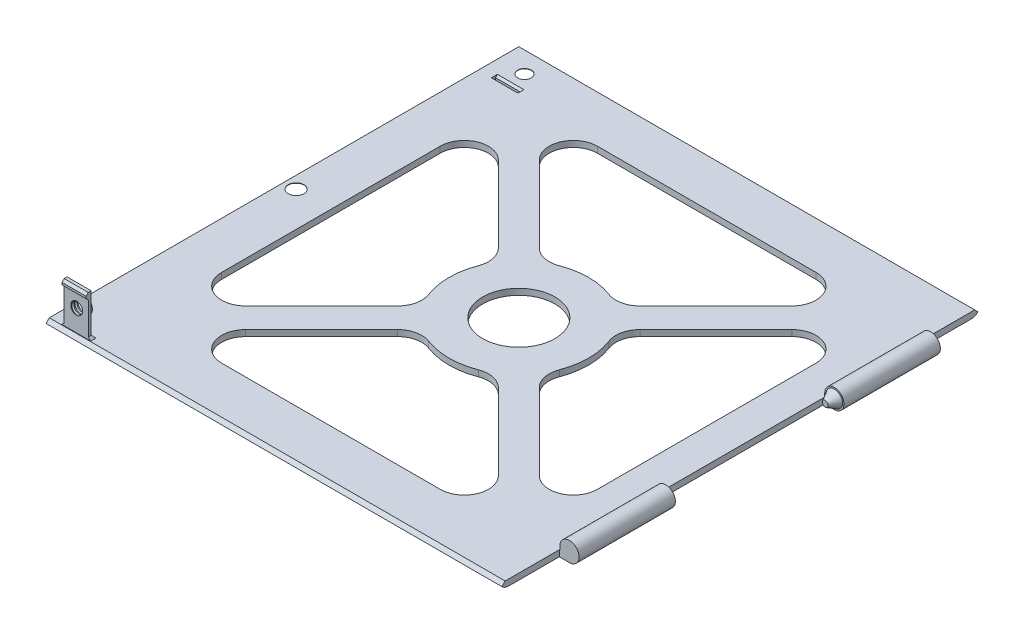
SolidWorks part; units mm, degrees
material "6061 Alloy"
ref_plane "Front Plane" through (0, 0, 0) normal (0, 0, 1) x (1, 0, 0)
ref_plane "Top Plane" through (0, 0, 0) normal (0, 1, 0) x (1, 0, 0)
ref_plane "Right Plane" through (0, 0, 0) normal (1, 0, 0) x (0, 0, -1)
sketch "X-Axis" plane through (0, 0, 0) normal (0, 1, 0) x (1, 0, 0)
  line L2 (-10, 0) -> (10, 0)
  point P3 (0, 0)
  dimension "D1" = 20
sketch "Y-Axis" plane through (0, 0, 0) normal (0, 1, 0) x (1, 0, 0)
  line L0 (0, -10) -> (0, 10)
  dimension "D1" = 20
sketch "Z-Axis" plane through (0, 0, 0) normal (1, 0, 0) x (0, 0, -1)
  line L0 (0, 10) -> (0, -10)
  line L1 (0, 55) -> (0, -55) construction
  point P5 (0, 0)
  dimension "D1" = 20
ref_axis "Axis1" through (0, 0, 0) along (0, 1, 0)
sketch "Sketch1" plane through (0, 0, 0) normal (0, 1, 0) x (1, 0, 0)
  line L0 (-10.4535, 14.6961) -> (-26.2218, 30.4645)
  line L1 (-46, -46) -> (46, -46) construction
  line L2 (-46, -46) -> (-46, 46) construction
  line L3 (-46, 46) -> (46, 46) construction
  line L4 (46, -46) -> (46, 46) construction
  line L5 (-46, -46) -> (46, 46) construction
  line L6 (-46, 46) -> (46, -46) construction
  line L7 (-22.6863, 39) -> (22.6863, 39)
  line L8 (26.2218, 30.4645) -> (10.4535, 14.6961)
  line L9 (30.4645, -26.2218) -> (14.6961, -10.4535)
  line L10 (14.6961, 10.4535) -> (30.4645, 26.2218)
  line L11 (39, 22.6863) -> (39, -22.6863)
  line L12 (-26.2218, -30.4645) -> (-10.4535, -14.6961)
  line L13 (10.4535, -14.6961) -> (26.2218, -30.4645)
  line L14 (22.6863, -39) -> (-22.6863, -39)
  line L15 (-30.4645, 26.2218) -> (-14.6961, 10.4535)
  line L16 (-14.6961, -10.4535) -> (-30.4645, -26.2218)
  line L17 (-39, -22.6863) -> (-39, 22.6863)
  line L19 (46, -50) -> (-46, -50)
  line L20 (46, -50) -> (46, 50)
  line L21 (46, 50) -> (-46, 50)
  line L22 (-46, -50) -> (-46, 50)
  line L23 (46, -50) -> (-46, 50) construction
  line L24 (46, 50) -> (-46, -50) construction
  circle A0 centre (0, 0) radius 7.5
  arc A1 (-5.1441, 13.5569) -> (5.1441, 13.5569) centre (0, 0) cw
  arc A2 (-5.1441, 13.5569) -> (-10.4535, 14.6961) centre (-6.9179, 18.2316) cw
  arc A3 (5.1441, 13.5569) -> (10.4535, 14.6961) centre (6.9179, 18.2316) ccw
  arc A4 (22.6863, 39) -> (26.2218, 30.4645) centre (22.6863, 34) cw
  arc A5 (-26.2218, 30.4645) -> (-22.6863, 39) centre (-22.6863, 34) cw
  arc A6 (13.5569, -5.1441) -> (14.6961, -10.4535) centre (18.2316, -6.9179) ccw
  arc A7 (13.5569, 5.1441) -> (13.5569, -5.1441) centre (0, 0) cw
  arc A8 (13.5569, 5.1441) -> (14.6961, 10.4535) centre (18.2316, 6.9179) cw
  arc A9 (30.4645, 26.2218) -> (39, 22.6863) centre (34, 22.6863) cw
  arc A10 (39, -22.6863) -> (30.4645, -26.2218) centre (34, -22.6863) cw
  arc A11 (-5.1441, -13.5569) -> (-10.4535, -14.6961) centre (-6.9179, -18.2316) ccw
  arc A12 (5.1441, -13.5569) -> (-5.1441, -13.5569) centre (0, 0) cw
  arc A13 (5.1441, -13.5569) -> (10.4535, -14.6961) centre (6.9179, -18.2316) cw
  arc A14 (26.2218, -30.4645) -> (22.6863, -39) centre (22.6863, -34) cw
  arc A15 (-22.6863, -39) -> (-26.2218, -30.4645) centre (-22.6863, -34) cw
  arc A16 (-13.5569, 5.1441) -> (-14.6961, 10.4535) centre (-18.2316, 6.9179) ccw
  arc A17 (-13.5569, -5.1441) -> (-13.5569, 5.1441) centre (0, 0) cw
  arc A18 (-13.5569, -5.1441) -> (-14.6961, -10.4535) centre (-18.2316, -6.9179) cw
  arc A19 (-30.4645, -26.2218) -> (-39, -22.6863) centre (-34, -22.6863) cw
  arc A20 (-39, 22.6863) -> (-30.4645, 26.2218) centre (-34, 22.6863) cw
  point P0 (0, 0)
  point P59 (0, 0)
  dimension "D3" = 15
  dimension "D6" = 7
  dimension "D8" = 5
  dimension "D1" = 92
  dimension "D2" = 92
  dimension "D4" = 6
  dimension "D5" = 6
  dimension "D7" = 39
  dimension "D10" = 100
  dimension "D9" = 4
extrude "Boss-Extrude1" add sketch "Sketch1" along normal blind 1.27
ref_plane "Plane3" through (0, 0, 17.5) normal (0, 0, 1) x (1, 0, 0)
sketch "Sketch6" plane through (0, 0, 17.5) normal (0, 0, 1) x (1, 0, 0)
  line L0 (46, 2) -> (46, 0)
  line L1 (46, 0) -> (48, 0)
  line L2 (0, 0) -> (0, 69.0457) construction
  arc A0 (46, 2) -> (48, 0) centre (48, 2) cw
  dimension "D1" = 50
extrude "Boss-Extrude3" add sketch "Sketch6" along normal blind 20
mirror "Mirror1" about plane through (0, 0, 0) normal (0, 0, 1) of "Boss-Extrude3"
sketch "Sketch16" plane through (0, 0, 17.5) normal (0, 0, -1) x (-1, 0, 0)
  circle A0 centre (-48, 2) radius 1.75
  dimension "D1" = 3.5
sketch "Sketch17" plane through (0, 0, -17.5) normal (0, 0, 1) x (1, 0, 0)
  circle A0 centre (48, 2) radius 1.7
  dimension "D1" = 3.4
extrude "Cut-Extrude5" cut sketch "Sketch16" against normal blind 2 draft 30 contours A0
extrude "Boss-Extrude7" add sketch "Sketch17" along normal blind 1.9 draft 30
sketch "Sketch23" plane through (0, 1.27, 0) normal (0, 1, 0) x (1, 0, 0)
  line L1 (-46, 50) -> (-49.5, 50)
  line L2 (-46, 50) -> (-46, -50)
  line L3 (-46, -50) -> (-49.5, -50)
  line L4 (-49.5, 50) -> (-49.5, -50)
  line L5 (50, 17.5) -> (50, 37.5) construction
  dimension "D1" = 99.5
extrude "Boss-Extrude9" add sketch "Sketch23" against normal up to surface (1.27 mm away) up to face at (0, 0, 24.6467)
sketch "Sketch21" plane through (46, 0, 0) normal (1, 0, 0) x (0, 0, -1)
  line L0 (-50, 0) -> (-47.5953, 2.4047) construction
  line L3 (-50, 0) -> (-37.5, 0) construction
  line L4 (-50, 1.27) -> (-50, 0) construction
  line L5 (-50, 1.27) -> (-37.5, 1.27) construction
  arc A0 (-50, 2) -> (-48, 0) centre (-48, 2) ccw
  dimension "D2" = 2
  dimension "D1" = 45
sketch "Sketch22" plane through (46, 0, 0) normal (1, 0, 0) x (0, 0, -1)
  line L0 (-48, 2) -> (-50.6263, -0.6263)
  line L2 (-50, 1.27) -> (-37.5, 1.27) construction
  point P0 (-48, 2)
  dimension "D1" = 45
extrude "Cut-Extrude7" cut sketch "Sketch22" against normal through all and the other way through all flip side to cut
extrude "Cut-Extrude8" cut sketch "Sketch21" against normal through all and the other way through all flip side to cut
sketch "Sketch24" plane through (0, 1.27, 0) normal (0, 1, 0) x (1, 0, 0)
  line L0 (46, -37.5) -> (50, -37.5) construction
  line L1 (46, -49.4142) -> (45.9, -49.4142)
  line L2 (46, -49.4142) -> (46, -37.5)
  line L3 (46, -37.5) -> (45.9, -37.5)
  line L4 (45.9, -49.4142) -> (45.9, -37.5)
  dimension "D1" = 0.1
extrude "Cut-Extrude9" cut sketch "Sketch24" against normal through all
mirror "Mirror2" about plane through (0, 0, 0) normal (0, 0, 1) of "Cut-Extrude8", "Cut-Extrude9", "Cut-Extrude7"
sketch "Sketch25" plane through (0, 1.27, 0) normal (0, 1, 0) x (1, 0, 0)
  line L1 (-49.5, -49.4142) -> (-48.73, -49.4142)
  line L2 (-49.5, -49.4142) -> (-49.5, -37.1142)
  line L3 (-49.5, -37.1142) -> (-48.73, -37.1142)
  line L4 (-48.73, -49.4142) -> (-48.73, -37.1142)
  line L5 (-49.5, 49.4142) -> (-48.73, 49.4142)
  line L6 (-49.5, 49.4142) -> (-49.5, 37.1142)
  line L7 (-49.5, 37.1142) -> (-48.73, 37.1142)
  line L8 (-48.73, 49.4142) -> (-48.73, 37.1142)
  dimension "D1" = 0.77
  dimension "D2" = 12.3
extrude "Cut-Extrude10" cut sketch "Sketch25" against normal through all
sketch "Sketch27" plane through (0, 1.27, 0) normal (0, 1, 0) x (1, 0, 0)
  line L1 (-45.73, -48.03) -> (-40.73, -48.03)
  line L2 (-45.73, -48.03) -> (-45.73, -48.63)
  line L3 (-45.73, -48.63) -> (-40.73, -48.63)
  line L4 (-40.73, -48.03) -> (-40.73, -48.63)
  line L5 (-48.73, -48.73) -> (-48.73, -37.1142) construction
  line L6 (45.9, -48.73) -> (-48.73, -48.73) construction
  dimension "D1" = 0.6
  dimension "D2" = 5
  dimension "D3" = 3
  dimension "D4" = 0.1
extrude "Boss-Extrude11" add sketch "Sketch27" along normal blind 8.5
sketch "Sketch28" plane through (-45.73, 0, 0) normal (-1, 0, 0) x (0, 0, 1)
  line L0 (48.63, 9.77) -> (49.0892, 9.3108)
  line L1 (49.0892, 9.3108) -> (49.0892, 8.8608)
  line L2 (49.0892, 8.8608) -> (48.63, 8.4016)
  line L3 (48.63, 9.77) -> (48.63, 1.27) construction
  line L4 (48.63, 8.4016) -> (48.63, 9.77)
  line L5 (48.03, 9.77) -> (48.63, 9.77) construction
  point P3 (49.0892, 9.0858)
  dimension "D1" = 0.45
  dimension "D2" = 0.6842
  dimension "D3" = 45
  dimension "D4" = 45
  dimension "D5" = 8.5
extrude "Boss-Extrude12" add sketch "Sketch28" against normal up to surface (5 mm away) up to face at (-40.73, 5.52, 48.33)
sketch "Sketch29" plane through (0, 1.27, 0) normal (0, 1, 0) x (1, 0, 0)
  line L1 (-45.98, 41.1392) -> (-40.48, 41.1392)
  line L2 (-45.98, 41.1392) -> (-45.98, 40.6892)
  line L3 (-45.98, 40.6892) -> (-40.48, 40.6892)
  line L4 (-40.48, 41.1392) -> (-40.48, 40.6892)
  line L8 (-40.73, -48.03) -> (-45.73, -48.03) construction
  line L9 (45.9, 49.4142) -> (-48.73, 49.4142) construction
  point P6 (-43.23, -48.03)
  point P7 (-45.98, 40.9142)
  point P11 (-43.23, 40.6892)
  dimension "D1" = 0.45
  dimension "D2" = 8.5
  dimension "D3" = 5.5
  dimension "D4" = 45.98
extrude "Cut-Extrude11" cut sketch "Sketch29" against normal through all
chamfer "Chamfer1" distance 0.4 angle 45 2 edges at (-43.23, 1.27, -40.6892) (-43.23, 1.27, -41.1392)
chamfer "Chamfer2" distance 0.5 angle 45 3 edges at (-40.73, 1.27, 48.33) (-43.23, 1.27, 48.03) (-45.73, 1.27, 48.33)
sketch "Sketch30" plane through (0, 0, 48.03) normal (0, 0, -1) x (-1, 0, 0)
  line L0 (40.73, 9.77) -> (45.73, 9.77) construction
  line L4 (40.73, 9.3108) -> (40.73, 8.8608) construction
  circle A0 centre (43.23, 5.5858) radius 1.75
  point P4 (43.23, 9.77)
  point P5 (40.73, 9.0858)
  dimension "D1" = 3.5
  dimension "D2" = 3.5
extrude "Boss-Extrude13" add sketch "Sketch30" along normal blind 1
hole_wizard "Tap Drill for #4-40 Tap1" positions "Sketch34" profile "Sketch33" hole size "#4-40" standard "ANSI Inch" end condition through all
sketch "Sketch34" plane through (0, 0, 47.03) normal (0, 0, -1) x (-1, 0, 0)
  point P0 (43.23, 5.5858)
sketch "Sketch33" plane through (-43.23, 5.5858, 47.03) normal (1, 0, 0) x (0, 1, 0)
  line L0 (0, 0) -> (0, 2.3842)
  line L1 (0, 2.3842) -> (1.1303, 2.3842)
  line L2 (1.1303, 2.3842) -> (1.1303, 0)
  line L5 (1.1303, 0) -> (0, 0)
  line L11 (0, -6.35) -> (0, 107.95) construction
  dimension "Thru Hole Dia." = 2.2606
  dimension "Thru Hole Depth" = 2.3842
ref_plane "Plane5" through (0, 0, 45.03) normal (0, 0, -1) x (-1, 0, 0)
sketch "Sketch35" plane through (0, 0, 45.03) normal (0, 0, -1) x (-1, 0, 0)
  circle A0 centre (43.23, 5.5858) radius 1.1303 construction
  circle A1 centre (43.23, 5.5858) radius 1.1303
curve "Helix/Spiral1" pitch 0.635 height 9.525 radius 1.1303 centre (-43.23, 5.5858, 45.03) axis (0, 0, 1) start towards (-1, 0, 0)
ref_plane "Plane6" through (-44.3603, 5.5858, 45.03) normal (0, -0.996, 0.0891) x (-1, 0, 0)
ref_axis "Axis2" through (-43.23, 5.5858, 47.03) along (0, 0, 1)
sketch "Sketch37" plane through (-44.3603, 5.5858, 45.03) normal (0, -0.996, 0.0891) x (-1, 0, 0)
  line L0 (0.2921, 0.0397) -> (0.2921, -0.0397)
  line L1 (0.2921, -0.0397) -> (-0.1079, -0.2706)
  line L2 (-0.1079, -0.2706) -> (-0.1079, 0.2706)
  line L3 (-0.1079, 0.2706) -> (0.2921, 0.0397)
  line L7 (-1.1303, -1.9921) -> (-1.1303, -2.9881) construction
  point P6 (0.2921, 0)
  point P7 (0, 0)
  dimension "D1" = 1.4224
  dimension "D2" = 60
  dimension "D3" = 60
  dimension "D4" = 0.0794
  dimension "D5" = 0.4
sweep "Cut-Sweep1" cut profiles "Sketch37" path "Helix/Spiral1"
sketch "Sketch32" plane through (0, 1.27, 0) normal (0, 1, 0) x (1, 0, 0)
  line L0 (-45.98, 40.6892) -> (-40.48, 40.6892) construction
  line L2 (-45.98, 41.5392) -> (-45.98, 40.2892) construction
  circle A0 centre (-43.23, 44.4142) radius 1.4046
  point P4 (-43.23, 40.6892)
  point P5 (-45.98, 40.9142)
  dimension "D1" = 2.8092
  dimension "D2" = 3.5
extrude "Cut-Extrude13" cut sketch "Sketch32" against normal through all
sketch "Sketch38" plane through (0, 1.27, 0) normal (0, 1, 0) x (1, 0, 0)
  line L1 (-49.5, 37.1142) -> (-48.73, 37.1142)
  line L2 (-49.5, 37.1142) -> (-49.5, -37.1142)
  line L3 (-49.5, -37.1142) -> (-48.73, -37.1142)
  line L4 (-48.73, 37.1142) -> (-48.73, -37.1142)
extrude "Cut-Extrude14" cut sketch "Sketch38" against normal through all
hole_wizard "#4 Clearance Hole1" positions "Sketch41" profile "Sketch40" hole size "#4" standard "ANSI Inch" end condition through all
sketch "Sketch41" plane through (0, 1.27, 0) normal (0, 1, 0) x (1, 0, 0)
  line L0 (-48.73, -48.73) -> (-48.73, 48.73) construction
  point P0 (-46.23, 0)
  dimension "D1" = 2.5
sketch "Sketch40" plane through (-46.23, 1.27, 0) normal (1, 0, 0) x (0, 0, 1)
  line L0 (0, 0) -> (0, 1.27)
  line L1 (0, 1.27) -> (1.6319, 1.27)
  line L2 (1.6319, 1.27) -> (1.6319, 0)
  line L5 (1.6319, 0) -> (0, 0)
  line L11 (0, -6.35) -> (0, 107.95) construction
  dimension "Thru Hole Dia." = 3.2639
  dimension "Thru Hole Depth" = 1.27
ref_axis "Axis3" through (-43.23, 0, -44.4142) along (0, 1, 0)
ref_plane "Plane7" through (0, 0, -44.4142) normal (0, 0, 1) x (1, 0, 0)
sketch "Sketch42" plane through (0, 0, -44.4142) normal (0, 0, 1) x (1, 0, 0)
  line L0 (-39.93, 0) -> (-40.9678, 1.1938) construction
  line L1 (-40.9678, 1.1938) -> (-43.23, 1.1938) construction
  line L2 (-45.4922, 1.1938) -> (-46.53, 0)
  line L3 (-46.53, 0) -> (-43.23, 0)
  line L5 (45.9, 0) -> (-48.73, 0) construction
  line L6 (-43.23, 1.1938) -> (-43.23, 0)
  line L7 (-43.23, 0) -> (-39.93, 0) construction
  line L8 (-43.23, 1.1938) -> (-45.4922, 1.1938)
  line L9 (-43.23, 0) -> (-43.23, 1.27) construction
  dimension "D1" = 82
  dimension "D2" = 1.1938
  dimension "D3" = 6.6
  dimension "D4" = 49
revolve "Cut-Revolve2" cut sketch "Sketch42" angle 360 about L6
ref_axis "Axis4" through (-46.23, 0, 0) along (0, 1, 0)
ref_plane "Plane8" through (-46.23, 0, 0) normal (-1, 0, 0) x (0, 0, 1)
sketch "Sketch43" plane through (-46.23, 0, 0) normal (-1, 0, 0) x (0, 0, 1)
  line L0 (0, 2.2877) -> (0, 1.1938) construction
  line L1 (0, 0) -> (0, 1.27) construction
  line L2 (0, 1.1938) -> (-2.2642, 1.1938)
  line L3 (-2.2642, 1.1938) -> (-3.302, 0)
  line L4 (48, 0) -> (-48, 0) construction
  line L5 (-3.302, 0) -> (0, 0)
  line L6 (0, 0) -> (0, 1.1938)
  dimension "D1" = 49
  dimension "D2" = 1.1938
  dimension "D3" = 6.604
revolve "Cut-Revolve3" cut sketch "Sketch43" angle 360 about L0
equation "\"D2@Sketch32\"=\"D2@Sketch30\""
equation "\"D2@Sketch29\"=\"D1@Boss-Extrude11\""
